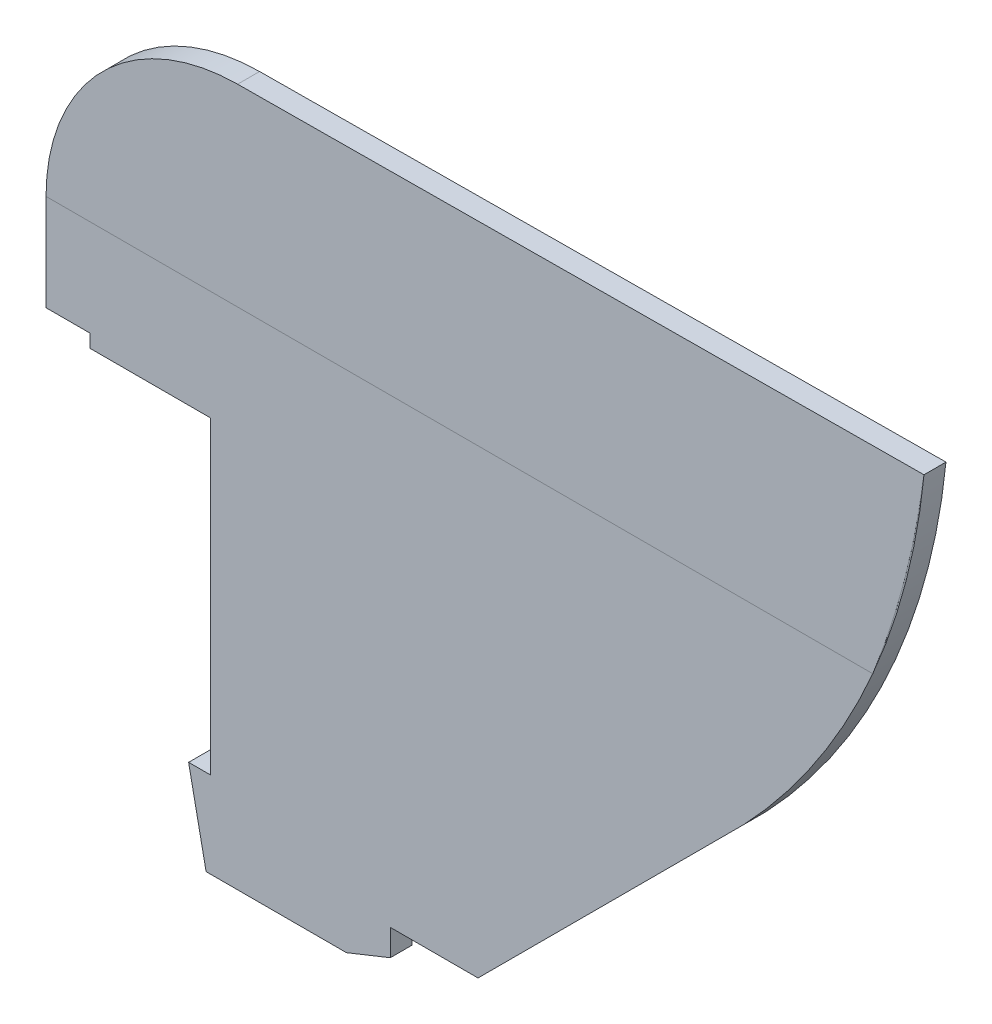
SolidWorks part; units mm, degrees
ref_plane "Plan de face" through (0, 0, 0) normal (0, 0, 1) x (1, 0, 0)
ref_plane "Plan de dessus" through (0, 0, 0) normal (0, 1, 0) x (1, 0, 0)
ref_plane "Plan de droite" through (0, 0, 0) normal (1, 0, 0) x (0, 0, -1)
sketch "Esquisse1" plane through (0, 0, 0) normal (0, 0, 1) x (1, 0, 0)
  line L0 (0, 0) -> (188.5, 0) construction
  line L1 (0, 0) -> (0, -25)
  line L2 (0, -25) -> (37.5, -25)
  line L3 (37.5, -25) -> (37.5, -95.5)
  line L4 (37.5, -95.5) -> (32.5, -95.5)
  line L5 (32.5, -95.5) -> (36.4874, -115.0985)
  line L6 (36.4874, -115.0985) -> (88.4874, -115.0985)
  line L7 (88.4874, -115.0985) -> (159.198, -44.3878)
  line L8 (43.6829, 43.9989) -> (200.1829, 45.1267)
  arc A0 (0, 0) -> (43.6829, 43.9989) centre (44, 0) cw
  arc A1 (159.198, -44.3878) -> (200.1829, 45.1267) centre (49.0805, 60.1702) ccw
  dimension "D11" = 44
  dimension "D1" = 188.5
  dimension "D2" = 25
  dimension "D3" = 37.5
  dimension "D4" = 90
  dimension "D5" = 70.5
  dimension "D6" = 5
  dimension "D7" = 20
  dimension "D8" = 52
  dimension "D9" = 135
  dimension "D10" = 100
  dimension "D12" = 156.5
extrude "Boss.-Extru.1" add sketch "Esquisse1" along normal blind 5
sketch "Esquisse2" plane through (0, 0, 5) normal (0, 0, 1) x (1, 0, 0)
  line L0 (0, 0) -> (188.5, 0)
  line L1 (200.1829, 45.1267) -> (43.6829, 43.9989)
  arc A0 (188.5, 0) -> (200.1829, 45.1267) centre (16.1609, 68.6928) ccw
  arc A1 (43.6829, 43.9989) -> (0, 0) centre (44, 0) ccw
  dimension "D1" = 188.5
extrude "Boss.-Extru.2" add sketch "Esquisse2" along normal blind 0.01
sketch "Esquisse3" plane through (0, 0, 5) normal (0, 0, 1) x (1, 0, 0)
  line L1 (0, -25) -> (10, -25)
  line L2 (0, -25) -> (0, -22)
  line L3 (0, -22) -> (10, -22)
  line L4 (10, -25) -> (10, -22)
  dimension "D1" = 10
  dimension "D2" = 3
extrude "Enlèv. mat.-Extru.1" cut sketch "Esquisse3" against normal through all
sketch "Esquisse4" plane through (0, 0, 5) normal (0, 0, 1) x (1, 0, 0)
  line L0 (88.4874, -115.0985) -> (88.4874, -105.0985) construction
  line L1 (88.4874, -105.0985) -> (78.4874, -105.0985)
  line L2 (78.4874, -105.0985) -> (78.4874, -115.0985) construction
  line L3 (36.4874, -115.0985) -> (88.4874, -115.0985) construction
  line L4 (78.4874, -115.0985) -> (88.4874, -115.0985)
  line L5 (88.4874, -105.0985) -> (98.4874, -105.0985)
  line L6 (88.4874, -115.0985) -> (159.198, -44.3878) construction
  line L7 (98.4874, -105.0985) -> (88.4874, -115.0985)
  line L8 (78.4874, -105.0985) -> (78.4874, -111.0985)
  line L9 (78.4874, -111.0985) -> (68.4874, -115.0985)
  line L10 (68.4874, -115.0985) -> (78.4874, -115.0985)
  dimension "D1" = 10
  dimension "D2" = 10
  dimension "D3" = 10
  dimension "D4" = 4
extrude "Enlèv. mat.-Extru.2" cut sketch "Esquisse4" against normal through all
